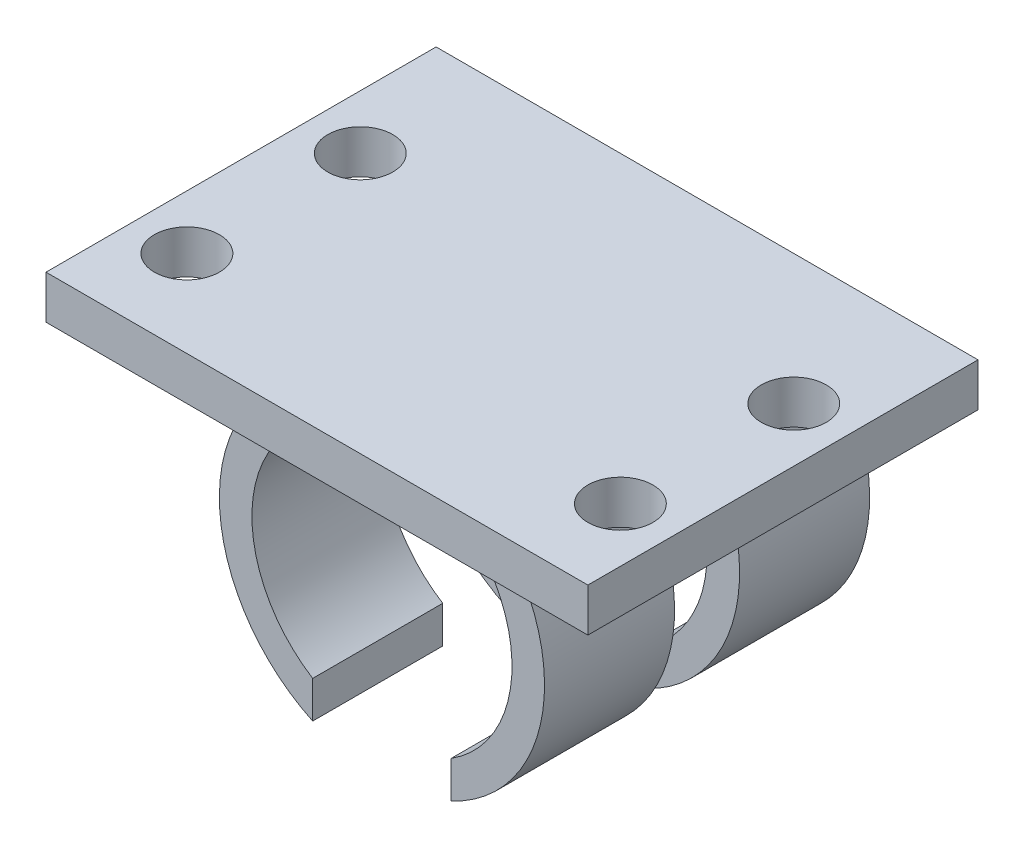
SolidWorks part; units mm, degrees
ref_plane "前视基准面" through (0, 0, 0) normal (0, 0, 1) x (1, 0, 0)
ref_plane "上视基准面" through (0, 0, 0) normal (0, 1, 0) x (1, 0, 0)
ref_plane "右视基准面" through (0, 0, 0) normal (1, 0, 0) x (0, 0, -1)
sketch "草图1" plane through (0, 0, 0) normal (0, 0, 1) x (1, 0, 0)
  line L0 (12.5007, 7.9993) -> (-12.5007, 8.0003)
  line L1 (-12.5007, 6) -> (12.5005, 5.999)
  line L5 (3.1955, -5.0783) -> (3.1953, -6.7853)
  line L6 (-3.1959, -5.078) -> (-3.1959, -6.785)
  line L7 (12.5007, 7.9993) -> (12.5005, 5.999)
  line L10 (-12.5007, 6) -> (-12.5007, 8.0003)
  line L19 (3.3168, 4.9999) -> (-3.3164, 5.0001)
  arc A0 (-3.1959, -5.078) -> (-3.3164, 5.0001) centre (0, 0) cw
  arc A1 (3.3168, 4.9999) -> (3.1955, -5.0783) centre (0, 0) cw
  arc A2 (-4.5, 6) -> (-3.1959, -6.785) centre (0, 0) ccw
  arc A3 (4.5005, 5.9996) -> (3.1953, -6.7853) centre (0, 0) cw
  point P5 (0, 7.9998)
extrude "凸台-拉伸1" add sketch "草图1" along normal blind 15 contours A3 A2 L6 A0 L19 A1 L5 region at (7.2651, -0.7419, 0)
sketch "草图2" plane through (0, 0, 0) normal (1, 0, 0) x (0, 0, -1)
  line L0 (-7.5, -6.7853) -> (-6, -6.7853)
  line L1 (-7.5, -6.7853) -> (-9, -6.7853)
  line L2 (-9, -6.7853) -> (-9, 3.2147)
  line L3 (-9, 3.2147) -> (-6, 3.2147)
  line L4 (-6, 3.2147) -> (-6, -6.7853)
extrude "切除-拉伸1" cut sketch "草图2" against normal mid plane 15
extrude "凸台-拉伸3" add sketch "草图1<4>" along normal blind 18 contours L10 L7 L0 region at (0, 6.9997, 0)
sketch "草图1<4>" plane through (0, 0, 0) normal (0, 0, 1) x (1, 0, 0) same geometry as "草图1"
sketch "草图3" plane through (0.0003, 7.9998, 0) normal (0, 1, 0) x (1, 0, 0)
  line L0 (0, -2) -> (-0.0003, -26) construction
  circle A0 centre (-10.001, -6) radius 1.5
  circle A1 centre (-10.001, -14) radius 1.5
  circle A3 centre (10.0009, -6.0003) radius 1.5
  circle A4 centre (10.0007, -14.0003) radius 1.5
extrude "切除-拉伸2" cut sketch "草图3" against normal blind 10
